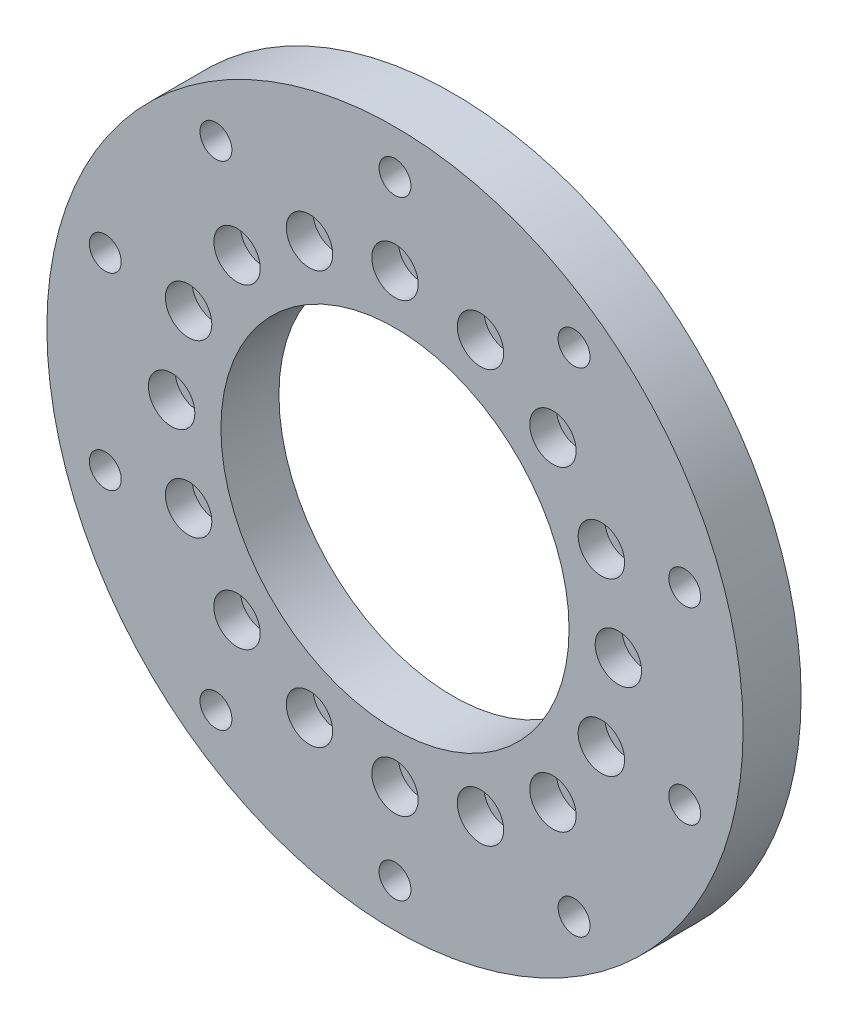
SolidWorks part; units mm, degrees
ref_plane "前视基准面" through (0, 0, 0) normal (0, 0, 1) x (1, 0, 0)
ref_plane "上视基准面" through (0, 0, 0) normal (0, 1, 0) x (1, 0, 0)
ref_plane "右视基准面" through (0, 0, 0) normal (1, 0, 0) x (0, 0, -1)
sketch "草图1" plane through (0, 0, 0) normal (0, 0, 1) x (1, 0, 0)
  circle A0 centre (0, 0) radius 60
  dimension "D1" = 120
extrude "凸台-拉伸1" add sketch "草图1" along normal blind 10
sketch "草图4" plane through (0, 0, 10) normal (0, 0, 1) x (1, 0, 0)
  circle A0 centre (0, 0) radius 30
  dimension "D1" = 60
extrude "切除-拉伸1" cut sketch "草图4" against normal through all
hole_wizard "打孔尺寸(%根据)内六角圆柱头螺钉的类型1" positions "草图3" profile "草图2" counterbore size "M4" standard "GB" end condition through all
sketch "草图3" plane through (0, 0, 10) normal (0, 0, 1) x (1, 0, 0)
  line L0 (0, 0) -> (0, 58.7) construction
  circle A0 centre (0, 0) radius 38.5 construction
  point P0 (0, 38.5)
  dimension "D1" = 77
sketch "草图2" plane through (0, 38.5, 10) normal (1, 0, 0) x (0, -1, 0)
  line L0 (0, 0) -> (0, 10)
  line L1 (0, 10) -> (2.25, 10)
  line L3 (2.25, 10) -> (2.25, 4.6)
  line L4 (2.25, 4.6) -> (4, 4.6)
  line L5 (4, 4.6) -> (4, 0)
  line L7 (4, 0) -> (0, 0)
  line L11 (0, -6.35) -> (0, 107.95) construction
  dimension "通孔孔直径" = 4.5
  dimension "通孔孔深度" = 10
  dimension "柱形沉头孔直径" = 8
  dimension "柱形沉头孔深度" = 4.6
ref_axis "基准轴1" through (0, 0, 0) along (0, 0, 1)
pattern_circular "阵列(圆周)1" count 16 over 360 about axis through (0, 0, 0) along (0, 0, 1) of "打孔尺寸(%根据)内六角圆柱头螺钉的类型1"
hole_wizard "打孔尺寸(%根据)内六角圆柱头螺钉的类型2" positions "草图6" profile "草图5" counterbore size "M5" standard "GB" end condition through all
sketch "草图6" plane through (0, 0, 0) normal (0, 0, -1) x (-1, 0, 0)
  line L0 (0, 0) -> (0, 63.6429) construction
  circle A0 centre (0, 0) radius 52.5 construction
  point P0 (0, 52.5)
  dimension "D1" = 105
sketch "草图5" plane through (0, 52.5, 0) normal (1, 0, 0) x (0, 1, 0)
  line L0 (0, 0) -> (0, 10)
  line L1 (0, 10) -> (2.75, 10)
  line L3 (2.75, 10) -> (2.75, 5.7)
  line L4 (2.75, 5.7) -> (5, 5.7)
  line L5 (5, 5.7) -> (5, 0)
  line L7 (5, 0) -> (0, 0)
  line L11 (0, -6.35) -> (0, 107.95) construction
  dimension "通孔孔直径" = 5.5
  dimension "通孔孔深度" = 10
  dimension "柱形沉头孔直径" = 10
  dimension "柱形沉头孔深度" = 5.7
pattern_circular "阵列(圆周)2" count 10 over 360 about axis through (0, 0, 0) along (0, 0, 1) of "打孔尺寸(%根据)内六角圆柱头螺钉的类型2"
